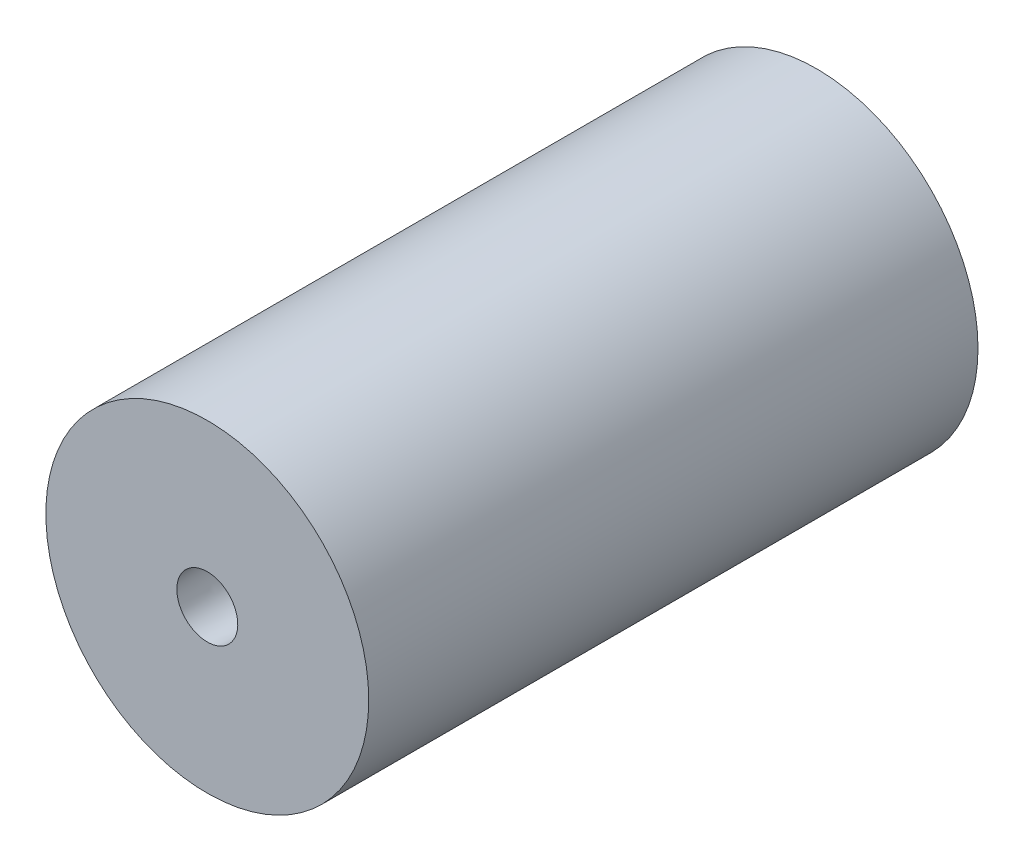
SolidWorks part; units mm, degrees
ref_plane "Front Plane" through (0, 0, 0) normal (0, 0, 1) x (1, 0, 0)
ref_plane "Top Plane" through (0, 0, 0) normal (0, 1, 0) x (1, 0, 0)
ref_plane "Right Plane" through (0, 0, 0) normal (1, 0, 0) x (0, 0, -1)
sketch "Sketch1" plane through (0, 0, 0) normal (0, 0, 1) x (1, 0, 0)
  circle A0 centre (0, 0) radius 2.65
  dimension "D1" = 5.3
extrude "Boss-Extrude1" add sketch "Sketch1" along normal blind 10 contours A0
sketch "Sketch2" plane through (0, 0, 10) normal (0, 0, 1) x (1, 0, 0)
  circle A0 centre (0, 0) radius 0.5
  dimension "D1" = 1
sketch "Sketch3" plane through (0, 0, 0) normal (0, 0, -1) x (-1, 0, 0)
  circle A0 centre (0, 0) radius 1
  dimension "D1" = 2
loft "Cut-Loft1" cut profiles "Sketch3", "Sketch2" connector at (0.958, 0.2868, 0) connector at (0.4623, -0.1905, 10)
